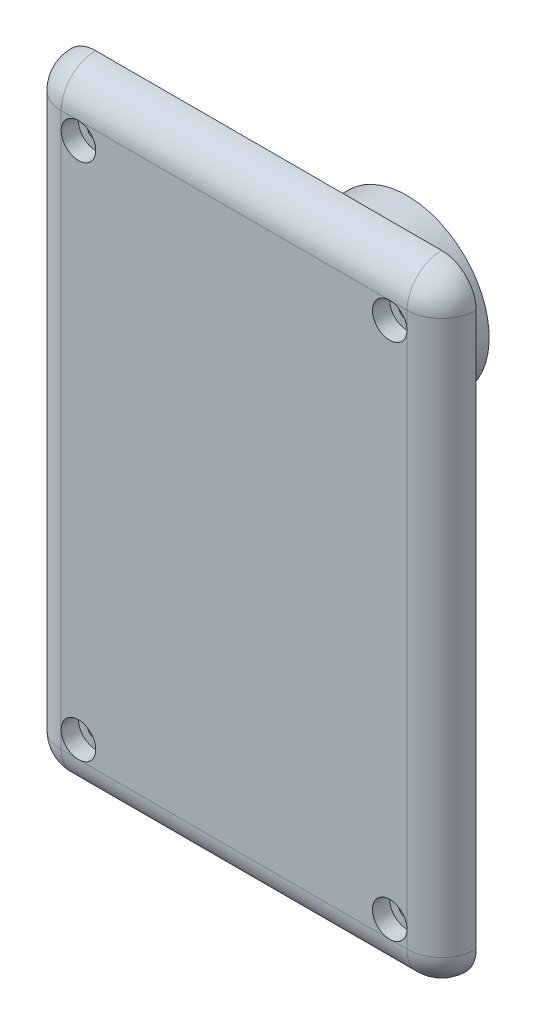
SolidWorks part; units mm, degrees
other "标注1"
sketch "草图6" plane through (-121.7901, 77.7286, -9) normal (-0.0529, 0.1135, -0.9921) x (-0.9984, 0.0112, 0.0545)
ref_plane "前视基准面" through (0, 0, 0) normal (0, 0, 1) x (1, 0, 0)
ref_plane "上视基准面" through (0, 0, 0) normal (0, 1, 0) x (1, 0, 0)
ref_plane "右视基准面" through (0, 0, 0) normal (1, 0, 0) x (0, 0, -1)
sketch "草图1" plane through (0, 0, 0) normal (0, 0, 1) x (1, 0, 0)
  line L1 (-97.7901, 77.7286) -> (-121.7901, 77.7286)
  line L2 (-97.7901, 77.7286) -> (-97.7901, 41.7286)
  line L3 (-97.7901, 41.7286) -> (-121.7901, 41.7286)
  line L4 (-121.7901, 77.7286) -> (-121.7901, 41.7286)
  dimension "D1" = 24
  dimension "D2" = 36
extrude "凸台-拉伸1" add sketch "草图1" along normal blind 2
fillet "圆角1" radius 2 4 edges at (-121.7901, 59.7286, 2) (-109.7901, 41.7286, 2) (-97.7901, 59.7286, 2) (-109.7901, 77.7286, 2)
sketch "草图4" plane through (0, 0, 0) normal (0, 0, -1) x (-1, 0, 0)
  line L0 (99.7901, 77.7286) -> (119.7901, 77.7286) construction
  line L2 (121.7901, 75.7286) -> (121.7901, 43.7286) construction
  circle A0 centre (117.4201, 66.2086) radius 2.05
  dimension "D1" = 11.52
  dimension "D3" = 4.1
  dimension "D2" = 4.37
extrude "切除-拉伸1" cut sketch "草图4" against normal blind 1
sketch "草图7" plane through (0, 0, 0) normal (0, 0, -1) x (-1, 0, 0)
  line L0 (99.7901, 77.7286) -> (119.7901, 77.7286) construction
  line L1 (97.7901, 43.7286) -> (97.7901, 75.7286) construction
  circle A0 centre (105.7901, 70.7286) radius 4
  circle A1 centre (105.7901, 70.7286) radius 4.75
  dimension "D1" = 8
  dimension "D2" = 9.5
  dimension "D3" = 7
  dimension "D4" = 8
extrude "凸台-拉伸2" add sketch "草图7" along normal blind 4
sketch "草图8" plane through (0, 0, -4) normal (0, 0, -1) x (-1, 0, 0)
  line L1 (107.295, 64.8064) -> (104.2968, 64.7052)
  line L2 (107.295, 64.8064) -> (107.295, 67.7052)
  line L3 (107.295, 67.7052) -> (104.2968, 67.7052)
  line L4 (104.2968, 64.7052) -> (104.2968, 67.7052)
  dimension "D1" = 3
  dimension "D2" = 3
extrude "切除-拉伸2" cut sketch "草图8" along a picked direction on the side against the normal blind 4
sketch "草图9" plane through (0, 0, 2) normal (0, 0, 1) x (1, 0, 0)
  line L0 (-97.7901, 43.7286) -> (-97.7901, 75.7286) construction
  line L2 (-119.7901, 41.7286) -> (-99.7901, 41.7286) construction
  line L3 (-99.7901, 77.7286) -> (-119.7901, 77.7286) construction
  line L4 (-121.7901, 75.7286) -> (-121.7901, 43.7286) construction
  circle A0 centre (-100.7901, 74.7286) radius 1
  circle A1 centre (-100.7901, 44.7286) radius 1
  circle A2 centre (-118.7901, 44.7286) radius 1
  circle A3 centre (-118.7901, 74.7286) radius 1
  dimension "D1" = 3
  dimension "D2" = 3
  dimension "D3" = 3
  dimension "D4" = 3
extrude "切除-拉伸3" cut sketch "草图9" against normal blind 1
sketch "草图10" plane through (0, 0, 1) normal (0, 0, 1) x (1, 0, 0)
  circle A0 centre (-118.7901, 44.7286) radius 0.5
  circle A1 centre (-100.7901, 44.7286) radius 0.5
  circle A2 centre (-100.7901, 74.7286) radius 0.5
  circle A3 centre (-118.7901, 74.7286) radius 0.5
  circle A5 centre (-118.7901, 74.7286) radius 1 construction
  circle A6 centre (-100.7901, 74.7286) radius 1 construction
  circle A7 centre (-118.7901, 44.7286) radius 1 construction
  circle A8 centre (-100.7901, 44.7286) radius 1 construction
  dimension "D1" = 1
extrude "切除-拉伸4" cut sketch "草图10" against normal up to next
sketch "草图12" plane through (0, 0, 0) normal (0, 0, -1) x (-1, 0, 0)
  line L0 (107.7414, 66.673) -> (111.0647, 59.5462) construction
  line L1 (108.1459, 66.8617) -> (111.4692, 59.7348)
  line L2 (107.3369, 66.4844) -> (110.6602, 59.3575)
  line L3 (119.7901, 41.7286) -> (99.7901, 41.7286) construction
  line L4 (107.295, 67.0225) -> (107.295, 66.2233) construction
  arc A0 (108.1459, 66.8617) -> (107.3369, 66.4844) centre (107.7414, 66.673) ccw
  arc A1 (110.6602, 59.3575) -> (111.4692, 59.7348) centre (111.0647, 59.5462) ccw
  point P2 (109.403, 63.1096)
  point P7 (0, 0)
  point P10 (0, 0)
  point P11 (0, 0)
  point P12 (0, 0)
  point P13 (0, 0)
  point P14 (0, 0)
  point P16 (0, 0)
  point P17 (0, 0)
  dimension "D1" = 65
extrude "凸台-拉伸3" add sketch "草图12" along normal blind 4 contours L2 A1 L1 A0
